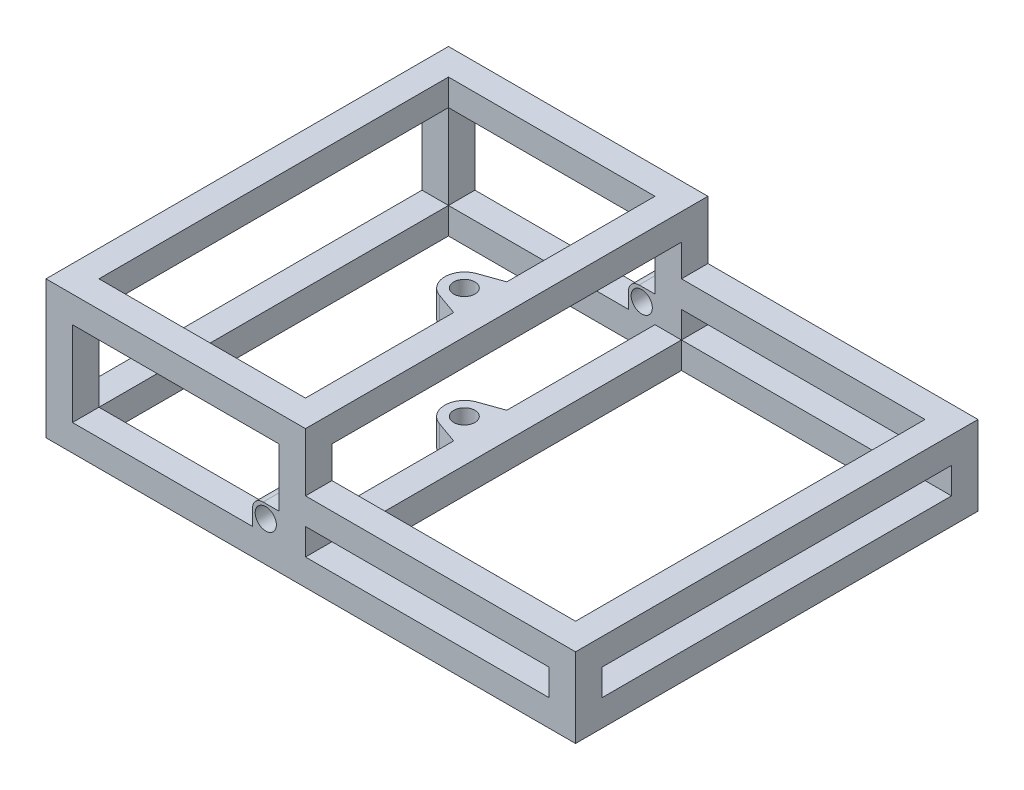
SolidWorks part; units mm, degrees
ref_plane "Front Plane" through (0, 0, 0) normal (0, 0, 1) x (1, 0, 0)
ref_plane "Top Plane" through (0, 0, 0) normal (0, 1, 0) x (1, 0, 0)
ref_plane "Right Plane" through (0, 0, 0) normal (1, 0, 0) x (0, 0, -1)
sketch "Sketch1" plane through (0, 0, 0) normal (0, 0, 1) x (1, 0, 0)
  line L0 (250, 10) -> (-5, 10)
  line L5 (250, -65) -> (-250, -65)
  line L6 (250, -65) -> (250, 65)
  line L7 (250, 65) -> (-250, 65)
  line L8 (-250, -65) -> (-250, 65)
  line L9 (250, -65) -> (-250, 65) construction
  line L10 (250, 65) -> (-250, -65) construction
  line L11 (-5, 10) -> (-5, 65)
  line L12 (-30, -15) -> (-55, -15)
  line L13 (-250, 40) -> (-5, 40)
  line L14 (-250, 40) -> (-250, 65)
  line L15 (-250, 65) -> (-5, 65)
  line L16 (-5, 40) -> (-5, 65)
  line L17 (-250, -65) -> (250, -65)
  line L18 (-250, -65) -> (-250, -40)
  line L19 (-250, -40) -> (250, -40)
  line L20 (250, -65) -> (250, -40)
  line L21 (250, 10) -> (-5, 10)
  line L22 (250, 10) -> (250, -15)
  line L23 (250, -15) -> (-5, -15)
  line L24 (-5, 10) -> (-5, -15)
  line L25 (-30, 40) -> (-5, 40)
  line L26 (-30, 40) -> (-30, -40)
  line L27 (-30, -40) -> (-5, -40)
  line L28 (-5, 40) -> (-5, -40)
  line L29 (-250, 40) -> (-225, 40)
  line L30 (-250, 40) -> (-250, -40)
  line L31 (-250, -40) -> (-225, -40)
  line L32 (-225, 40) -> (-225, -40)
  line L33 (250, -40) -> (225, -40)
  line L34 (250, -40) -> (250, -15)
  line L35 (250, -15) -> (225, -15)
  line L36 (225, -40) -> (225, -15)
  line L37 (-55, -40) -> (-55, -15)
  line L38 (-42.5, -27.5) -> (-42.5, -15) construction
  line L39 (-55, -27.5) -> (-42.5, -27.5) construction
  circle A0 centre (-42.5, -27.5) radius 10
  point P0 (0, 0)
  point P4 (12.5, -27.5)
  dimension "D11" = 20
  dimension "D1" = 500
  dimension "D2" = 130
  dimension "D4" = 255
  dimension "D3" = 25
  dimension "D5" = 25
  dimension "D6" = 25
  dimension "D7" = 25
  dimension "D8" = 25
  dimension "D9" = 25
  dimension "D10" = 75
  dimension "D12" = 25
extrude "Boss-Extrude1" add sketch "Sketch1" along normal blind 380 contours L0 L11 L7 L8 L5 L6 | L37 L19 L26 L12 A0 | L22 L21 L24 L23 | L34 L33 L36 L35 | L18 L17 L20 L19 | L30 L29 L32 L31 | L14 L13 L16 L15 | L25 L26 L27 L28 region at (0, -52.5, 0) region at (-30.3536, -27.5, 0)
fillet "Fillet1" radius 10 1 edges at (-55, -15, 190)
sketch "Sketch2" plane through (0, 65, 0) normal (0, 1, 0) x (1, 0, 0)
  line L0 (-5, 0) -> (-250, 0) construction
  line L1 (-250, 0) -> (-250, -380) construction
  line L2 (-250, -380) -> (-5, -380) construction
  line L3 (-5, -380) -> (-5, 0) construction
  line L4 (250, 0) -> (-5, 0) construction
  line L5 (-5, 0) -> (-5, -380) construction
  line L6 (-5, -380) -> (250, -380) construction
  line L7 (250, -380) -> (250, 0) construction
  line L8 (250, 0) -> (-5, 0)
  line L9 (-5, 0) -> (-5, -380)
  line L10 (-5, -380) -> (250, -380)
  line L11 (250, -380) -> (250, 0)
  line L12 (-5, 0) -> (-250, 0)
  line L13 (-250, 0) -> (-250, -380)
  line L14 (-250, -380) -> (-5, -380)
  line L15 (-5, -380) -> (-5, 0)
  line L16 (-225, -25) -> (-225, -355)
  line L21 (-225, -355) -> (-30, -355)
  line L22 (-30, -25) -> (-30, -355)
  line L23 (-30, -25) -> (-225, -25)
  line L28 (-5, -25) -> (225, -25)
  line L29 (225, -25) -> (225, -355)
  line L30 (225, -355) -> (-5, -355)
  line L31 (-30, -164.9359) -> (-50.9853, -172.3684)
  line L34 (25, -190) -> (289.3766, -190) construction
  line L40 (-30, -215.0641) -> (-50.9853, -207.6316)
  circle A0 centre (-45, -190) radius 10
  arc A1 (-50.9853, -172.3684) -> (-50.9853, -207.6316) centre (-44.7406, -190) ccw
  point P19 (-30, -190)
  point P22 (8.2028, -190.233)
  point P25 (-5.9242, -180.4301)
  point P26 (25, -228.7354)
  point P27 (12.7599, -190.3974)
  point P28 (0, -179.952)
  point P29 (-70.1795, -190)
  point P30 (-73.8252, -190)
  point P31 (-30, -277.0408)
  point P32 (-42.8368, -190)
  point P33 (0, 0)
  point P34 (-57.8753, -179.9744)
  point P35 (-30, -164.9359)
  point P36 (0, 0)
  point P37 (-50.9853, -207.6316)
  line M18 (-5, -380) -> (-5, 0)
  dimension "D3" = 25
  dimension "D4" = 20
  dimension "D2" = 25
  dimension "D5" = 15
  dimension "D1" = 25
extrude "Cut-Extrude1" cut sketch "Sketch2" against normal through all contours L34 L16 L21 L22 L40 A1 | L16 L34 A1 L31 L22 L23 | L34 L29 L28 M18 | L34 L15 L30 L29 region at (110, 65, 29.0224) region at (-129.1055, 65, 190)
sketch "Sketch3" plane through (250, 0, 0) normal (1, 0, 0) x (0, 0, -1)
  line L8 (-25, -40) -> (-25, -15)
  line L9 (-25, -15) -> (-355, -15)
  line L10 (-355, -15) -> (-355, -40)
  line L11 (-355, -40) -> (-25, -40)
  line L12 (-25, -40) -> (-25, -15)
  line L13 (-25, -15) -> (-355, -15)
  line L14 (-355, -15) -> (-355, -40)
  line L15 (-355, -40) -> (-25, -40)
  dimension "D1" = 25
extrude "Cut-Extrude2" cut sketch "Sketch3" against normal up to surface (25 mm away) up to face at (225, -27.5, 190)
sketch "Sketch4" plane through (-250, 0, 0) normal (-1, 0, 0) x (0, 0, 1)
  line L8 (355, 40) -> (25, 40)
  line L9 (25, 40) -> (25, -40)
  line L10 (25, -40) -> (355, -40)
  line L11 (355, -40) -> (355, 40)
  line L12 (355, 40) -> (25, 40)
  line L13 (25, 40) -> (25, -40)
  line L14 (25, -40) -> (355, -40)
  line L15 (355, -40) -> (355, 40)
  dimension "D1" = 25
extrude "Cut-Extrude3" cut sketch "Sketch4" against normal up to surface (245 mm away) contours L14 L15 L12 L13 region at (-250, 0, 190) up to face at (-5, -11.25, 190)
extrude "Cut-Extrude4" cut sketch "Sketch2<3>" against normal through all contours L34 A0 | A0 L34 region at (-45, 65, 190)
sketch "Sketch2<3>" plane through (0, 65, 0) normal (0, 1, 0) x (1, 0, 0) same geometry as "Sketch2"
equation "\"Rover_Length\"= 25in"
equation "\"Rover_Width\"= 18in"
equation "\"Rover_Height\"= 12in"
equation "\"Chassis_Wheelbase\"= 28in"
equation "\"Chassis_WheelDiam\"= 171mm"
equation "\"Chassis_ArmDiamWidth\"= 0.75in"
equation "\"Chassis_ArmAngle\"= 135deg"
equation "\"Chassis_ArmHeight\"= 8in"
equation "\"Chassis_HubMountOD\"= 3in"
equation "\"Chassis_WheelBoltHole\"= 36mm"
equation "\"Chassis_WheelBoltNum\"= 4"
equation "\"Chassis_DiffBarLength\"= 12in"
equation "\"Chassis_DiffBarWidth\"= 1in"
equation "\"Chassis_DiffBarHeight\"= 0.5in"
equation "\"Chassis_DiffLinkage_Length\"= 2.5in"
equation "\"Chassis_MountBracketThickness\"= 0.125in"
equation "\"Chassis_MountBracketWidth\"= 3in"
equation "\"Chassis_MountBacketOverlap\"= 0.5in"
equation "\"Chassis_ArmShaftDiam\"= 0.75in"
equation "\"Chassis_ArmHoleSpacing\" = 1.25in"
equation "\"Chassis_Length\" = 500mm"
equation "\"Chassis_Width\" = 380mm"
equation "\"Chassis_Thickness\" = 130mm"
equation "\"D1@Boss-Extrude1\"=\"Chassis_Width\""
equation "\"D2@Sketch1\"=\"Chassis_Thickness\""
equation "\"Chassis_Mod_Mount_Length\" = 255mm"
equation "\"D4@Sketch1\"=\"Chassis_Mod_Mount_Length\""
equation "\"Chassis_Extrusion_Profile\" = 25mm"
equation "\"D3@Sketch1\"=\"Chassis_Extrusion_Profile\""
equation "\"D5@Sketch1\"=\"Chassis_Extrusion_Profile\""
equation "\"D6@Sketch1\"=\"Chassis_Extrusion_Profile\""
equation "\"D7@Sketch1\"=\"Chassis_Extrusion_Profile\""
equation "\"D8@Sketch1\"=\"Chassis_Extrusion_Profile\""
equation "\"D9@Sketch1\"=\"Chassis_Extrusion_Profile\""
equation "\"D1@Sketch2\"=\"Chassis_Extrusion_Profile\""
equation "\"D2@Sketch2\"=\"Chassis_Extrusion_Profile\""
equation "\"D1@Sketch3\"=\"Chassis_Extrusion_Profile\""
equation "\"D1@Sketch4\"=\"Chassis_Extrusion_Profile\""
equation "\"D3@Sketch2\"=\"Chassis_Extrusion_Profile\""
equation "\"D1@Sketch1\"=\"Chassis_Length\""
